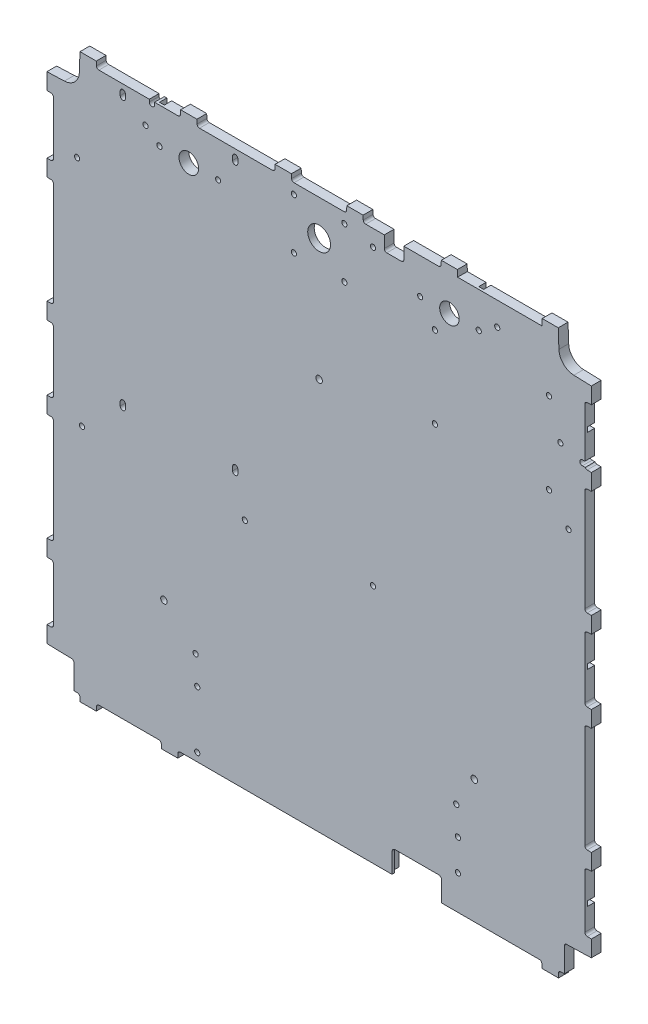
SolidWorks part; units mm, degrees
ref_plane "Alzado" through (0, 0, 0) normal (0, 0, 1) x (1, 0, 0)
ref_plane "Planta" through (0, 0, 0) normal (0, 1, 0) x (1, 0, 0)
ref_plane "Vista lateral" through (0, 0, 0) normal (1, 0, 0) x (0, 0, -1)
ref_plane "Plano1" through (0, 0, -3) normal (0, 0, -1) x (-1, 0, 0)
sketch "Croquis1" plane through (0, 0, -3) normal (0, 0, -1) x (-1, 0, 0)
  line L0 (-167.1, -152) -> (-154.0079, -152.4572)
  line L1 (-154.0079, -152.4572) -> (154.0079, -152.4572)
  line L2 (154.0079, -152.4572) -> (167.1, -152)
  line L3 (167.1, -152) -> (167.1, 172.8)
  line L4 (167.1, 172.8) -> (-167.1, 172.8)
  line L5 (-167.1, 172.8) -> (-167.1, -152)
  dimension "D1" = 13.0921
  dimension "D2" = 321.1079
  dimension "D3" = 334.2
  dimension "D4" = 0.4572
  dimension "D5" = 325.2572
extrude "Saliente-Extruir1" add sketch "Croquis1" against normal blind 6
sketch "Croquis2" plane through (0, -152.4572, 0) normal (0, -1, 0) x (1, 0, 0)
  line L0 (-150.5, 3) -> (150.5, 3)
  line L1 (150.5, 3) -> (150.5, -3)
  line L2 (150.5, -3) -> (-150.5, -3)
  line L3 (-150.5, -3) -> (-150.5, 3)
  line L4 (154.0079, 3) -> (154.0079, -3) construction
  line L5 (154.0079, -3) -> (-154.0079, -3) construction
  dimension "D1" = 3.5079
  dimension "D2" = 304.5079
  dimension "D3" = 6
extrude "Saliente-Extruir2" add sketch "Croquis2" along normal blind 20.3428
sketch "Croquis3" plane through (0, 0, 3) normal (0, 0, 1) x (1, 0, 0)
  line L0 (-136.6603, -172.8) -> (-96.9397, -172.8)
  line L1 (-96.9397, -172.8) -> (-96.9397, -168.8)
  line L2 (-96.9397, -168.8) -> (-136.6603, -168.8)
  line L3 (-136.6603, -168.8) -> (-136.6603, -172.8)
  line L4 (-167.1, -152) -> (-167.1, 172.8) construction
  line L5 (-167.1, 172.8) -> (167.1, 172.8) construction
  dimension "D1" = 30.4397
  dimension "D2" = 70.1603
  dimension "D3" = 341.6
  dimension "D4" = 345.6
extrude "Cortar-Extruir1" cut sketch "Croquis3" against normal through all
sketch "Croquis4" plane through (0, 0, 3) normal (0, 0, 1) x (1, 0, 0)
  line L0 (-167.1, -106.1397) -> (-167.1, -141.8603)
  line L1 (-167.1, -141.8603) -> (-163.1, -141.8603)
  line L2 (-163.1, -141.8603) -> (-163.1, -106.1397)
  line L3 (-163.1, -106.1397) -> (-167.1, -106.1397)
  line L4 (-136.6603, -168.8) -> (-136.6603, -172.8) construction
  line L5 (150.5, -172.8) -> (-96.9397, -172.8) construction
  dimension "D1" = 26.4397
  dimension "D2" = 30.4397
  dimension "D3" = 30.9397
  dimension "D4" = 66.6603
extrude "Cortar-Extruir2" cut sketch "Croquis4" against normal through all
sketch "Croquis5" plane through (0, 0, 3) normal (0, 0, 1) x (1, 0, 0)
  line L0 (-167.1, 19.8603) -> (-167.1, -19.8603)
  line L1 (-167.1, -19.8603) -> (-163.1, -19.8603)
  line L2 (-163.1, -19.8603) -> (-163.1, 19.8603)
  line L3 (-163.1, 19.8603) -> (-167.1, 19.8603)
  line L4 (-167.1, -152) -> (-167.1, -141.8603) construction
  line L5 (-136.6603, -172.8) -> (-150.5, -172.8) construction
  dimension "D1" = 4
  dimension "D2" = 152.9397
  dimension "D3" = 192.6603
extrude "Cortar-Extruir3" cut sketch "Croquis5" against normal through all
sketch "Croquis6" plane through (0, 0, 3) normal (0, 0, 1) x (1, 0, 0)
  line L0 (-167.1, 141.8603) -> (-167.1, 106.1397)
  line L1 (-167.1, 106.1397) -> (-163.1, 106.1397)
  line L2 (-163.1, 106.1397) -> (-163.1, 141.8603)
  line L3 (-163.1, 141.8603) -> (-167.1, 141.8603)
  line L4 (-167.1, -152) -> (-167.1, -141.8603) construction
  line L5 (-150.5, -152.4572) -> (-154.0079, -152.4572) construction
  dimension "D1" = 4
  dimension "D2" = 258.5969
  dimension "D3" = 294.3175
extrude "Cortar-Extruir4" cut sketch "Croquis6" against normal through all
sketch "Croquis7" plane through (0, 0, 3) normal (0, 0, 1) x (1, 0, 0)
  line L0 (-85, 172.8) -> (-136.8, 172.8)
  line L1 (-136.8, 172.8) -> (-136.8, 168.8)
  line L2 (-136.8, 168.8) -> (-85, 168.8)
  line L3 (-85, 168.8) -> (-85, 172.8)
  line L4 (-167.1, 19.8603) -> (-167.1, 106.1397) construction
  line L5 (-167.1, -141.8603) -> (-163.1, -141.8603) construction
  dimension "D1" = 30.3
  dimension "D2" = 82.1
  dimension "D3" = 310.6603
  dimension "D4" = 314.6603
extrude "Cortar-Extruir5" cut sketch "Croquis7" against normal through all
sketch "Croquis8" plane through (0, 0, -3) normal (0, 0, -1) x (-1, 0, 0)
  line L0 (-167.1, 124.5) -> (-156.779, 124.5)
  line L1 (-155.3, 123.25) -> (-153.9, 123.25)
  line L2 (-152.421, 124.5) -> (-152.421, 127.5)
  line L3 (-153.9, 128.75) -> (-155.3, 128.75)
  line L4 (-156.779, 127.5) -> (-167.1, 127.5)
  line L5 (-167.1, 127.5) -> (-167.1, 124.5)
  line L6 (-167.1, 172.8) -> (-167.1, -152) construction
  line L7 (85, 172.8) -> (-167.1, 172.8) construction
  arc A0 (-156.779, 124.5) -> (-155.3, 123.25) centre (-155.3, 124.75) ccw
  arc A1 (-153.9, 123.25) -> (-152.421, 124.5) centre (-153.9, 124.75) ccw
  arc A2 (-152.421, 127.5) -> (-153.9, 128.75) centre (-153.9, 127.25) ccw
  arc A3 (-155.3, 128.75) -> (-156.779, 127.5) centre (-155.3, 127.25) ccw
  dimension "D1" = 1.5
  dimension "D2" = 1.5
  dimension "D3" = 14.679
  dimension "D4" = 45.55
extrude "Cortar-Extruir6" cut sketch "Croquis8" against normal blind 4.5
sketch "Croquis9" plane through (0, 0, -3) normal (0, 0, -1) x (-1, 0, 0)
  line L0 (-115.3, -172.8) -> (-115.3, -162.479)
  line L1 (-114.05, -161) -> (-114.05, -159.6)
  line L2 (-115.3, -158.121) -> (-118.3, -158.121)
  line L3 (-119.55, -159.6) -> (-119.55, -161)
  line L4 (-118.3, -162.479) -> (-118.3, -172.8)
  line L5 (-118.3, -172.8) -> (-115.3, -172.8)
  line L6 (-167.1, 124.5) -> (-167.1, -152) construction
  line L7 (96.9397, -172.8) -> (-150.5, -172.8) construction
  arc A0 (-115.3, -162.479) -> (-114.05, -161) centre (-115.55, -161) ccw
  arc A1 (-114.05, -159.6) -> (-115.3, -158.121) centre (-115.55, -159.6) ccw
  arc A2 (-118.3, -158.121) -> (-119.55, -159.6) centre (-118.05, -159.6) ccw
  arc A3 (-119.55, -161) -> (-118.3, -162.479) centre (-118.05, -161) ccw
  dimension "D1" = 1.5
  dimension "D2" = 1.5
  dimension "D3" = 47.55
  dimension "D4" = 11.8
extrude "Cortar-Extruir7" cut sketch "Croquis9" against normal blind 4.5
sketch "Croquis10" plane through (0, 0, -3) normal (0, 0, -1) x (-1, 0, 0)
  line L0 (118.3, -168.8) -> (118.3, -162.479)
  line L1 (119.55, -161) -> (119.55, -159.6)
  line L2 (118.3, -158.121) -> (115.3, -158.121)
  line L3 (114.05, -159.6) -> (114.05, -161)
  line L4 (115.3, -162.479) -> (115.3, -168.8)
  line L5 (115.3, -168.8) -> (118.3, -168.8)
  line L6 (167.1, -152) -> (167.1, -141.8603) construction
  line L7 (150.5, -172.8) -> (136.6603, -172.8) construction
  arc A0 (118.3, -162.479) -> (119.55, -161) centre (118.05, -161) ccw
  arc A1 (119.55, -159.6) -> (118.3, -158.121) centre (118.05, -159.6) ccw
  arc A2 (115.3, -158.121) -> (114.05, -159.6) centre (115.55, -159.6) ccw
  arc A3 (114.05, -161) -> (115.3, -162.479) centre (115.55, -161) ccw
  dimension "D1" = 1.5
  dimension "D2" = 1.5
  dimension "D3" = 47.55
  dimension "D4" = 51.55
  dimension "D5" = 4
  dimension "D6" = 11.8
  dimension "D7" = 13.2
extrude "Cortar-Extruir8" cut sketch "Croquis10" against normal blind 4.5
sketch "Croquis11" plane through (0, 0, -3) normal (0, 0, -1) x (-1, 0, 0)
  line L0 (163.1, -124.5) -> (156.779, -124.5)
  line L1 (155.3, -123.25) -> (153.9, -123.25)
  line L2 (152.421, -124.5) -> (152.421, -127.5)
  line L3 (153.9, -128.75) -> (155.3, -128.75)
  line L4 (156.779, -127.5) -> (163.1, -127.5)
  line L5 (163.1, -127.5) -> (163.1, -124.5)
  line L6 (167.1, 141.8603) -> (167.1, 172.8) construction
  line L7 (167.1, 172.8) -> (136.8, 172.8) construction
  arc A0 (156.779, -124.5) -> (155.3, -123.25) centre (155.3, -124.75) ccw
  arc A1 (153.9, -123.25) -> (152.421, -124.5) centre (153.9, -124.75) ccw
  arc A2 (152.421, -127.5) -> (153.9, -128.75) centre (153.9, -127.25) ccw
  arc A3 (155.3, -128.75) -> (156.779, -127.5) centre (155.3, -127.25) ccw
  dimension "D1" = 1.5
  dimension "D2" = 1.5
  dimension "D3" = 4
  dimension "D4" = 296.05
  dimension "D5" = 297.3
  dimension "D6" = 300.05
extrude "Cortar-Extruir9" cut sketch "Croquis11" against normal blind 4.5
sketch "Croquis12" plane through (0, 0, -3) normal (0, 0, -1) x (-1, 0, 0)
  line L0 (163.1, 1.5) -> (156.779, 1.5)
  line L1 (155.3, 2.75) -> (153.9, 2.75)
  line L2 (152.421, 1.5) -> (152.421, -1.5)
  line L3 (153.9, -2.75) -> (155.3, -2.75)
  line L4 (156.779, -1.5) -> (163.1, -1.5)
  line L5 (163.1, -1.5) -> (163.1, 1.5)
  line L6 (167.1, 141.8603) -> (167.1, 172.8) construction
  line L7 (167.1, 172.8) -> (136.8, 172.8) construction
  arc A0 (156.779, 1.5) -> (155.3, 2.75) centre (155.3, 1.25) ccw
  arc A1 (153.9, 2.75) -> (152.421, 1.5) centre (153.9, 1.25) ccw
  arc A2 (152.421, -1.5) -> (153.9, -2.75) centre (153.9, -1.25) ccw
  arc A3 (155.3, -2.75) -> (156.779, -1.5) centre (155.3, -1.25) ccw
  dimension "D1" = 1.5
  dimension "D2" = 1.5
  dimension "D3" = 4
  dimension "D4" = 170.05
  dimension "D5" = 171.3
  dimension "D6" = 174.05
extrude "Cortar-Extruir10" cut sketch "Croquis12" against normal blind 4.5
sketch "Croquis13" plane through (0, 0, -3) normal (0, 0, -1) x (-1, 0, 0)
  line L0 (163.1, 127.5) -> (156.779, 127.5)
  line L1 (155.3, 128.75) -> (153.9, 128.75)
  line L2 (152.421, 127.5) -> (152.421, 124.5)
  line L3 (153.9, 123.25) -> (155.3, 123.25)
  line L4 (156.779, 124.5) -> (163.1, 124.5)
  line L5 (163.1, 124.5) -> (163.1, 127.5)
  line L6 (167.1, 141.8603) -> (167.1, 172.8) construction
  line L7 (167.1, 172.8) -> (136.8, 172.8) construction
  arc A0 (156.779, 127.5) -> (155.3, 128.75) centre (155.3, 127.25) ccw
  arc A1 (153.9, 128.75) -> (152.421, 127.5) centre (153.9, 127.25) ccw
  arc A2 (152.421, 124.5) -> (153.9, 123.25) centre (153.9, 124.75) ccw
  arc A3 (155.3, 123.25) -> (156.779, 124.5) centre (155.3, 124.75) ccw
  dimension "D1" = 1.5
  dimension "D2" = 1.5
  dimension "D3" = 4
  dimension "D4" = 44.05
  dimension "D5" = 45.3
  dimension "D6" = 48.05
extrude "Cortar-Extruir11" cut sketch "Croquis13" against normal blind 4.5
sketch "Croquis14" plane through (0, 0, -3) normal (0, 0, -1) x (-1, 0, 0)
  line L0 (96.5, 168.8) -> (96.5, 162.479)
  line L1 (95.25, 161) -> (95.25, 159.6)
  line L2 (96.5, 158.121) -> (99.5, 158.121)
  line L3 (100.75, 159.6) -> (100.75, 161)
  line L4 (99.5, 162.479) -> (99.5, 168.8)
  line L5 (99.5, 168.8) -> (96.5, 168.8)
  line L6 (167.1, 141.8603) -> (167.1, 172.8) construction
  line L7 (167.1, 172.8) -> (136.8, 172.8) construction
  arc A0 (96.5, 162.479) -> (95.25, 161) centre (96.75, 161) ccw
  arc A1 (95.25, 159.6) -> (96.5, 158.121) centre (96.75, 159.6) ccw
  arc A2 (99.5, 158.121) -> (100.75, 159.6) centre (99.25, 159.6) ccw
  arc A3 (100.75, 161) -> (99.5, 162.479) centre (99.25, 161) ccw
  dimension "D1" = 1.5
  dimension "D2" = 1.5
  dimension "D3" = 66.35
  dimension "D4" = 67.6
  dimension "D5" = 70.6
  dimension "D6" = 4
  dimension "D7" = 11.8
  dimension "D8" = 14.679
extrude "Cortar-Extruir12" cut sketch "Croquis14" against normal blind 4.5
sketch "Croquis15" plane through (0, 0, 3) normal (0, 0, 1) x (1, 0, 0)
  line L0 (44.75, -172.8) -> (136.8, -172.8)
  line L1 (136.8, -172.8) -> (136.8, -168.8)
  line L2 (136.8, -168.8) -> (75.25, -168.8)
  line L3 (75.25, -168.8) -> (75.25, -154.7)
  line L4 (75.25, -154.7) -> (44.75, -154.7)
  line L5 (44.75, -154.7) -> (44.75, -172.8)
  line L6 (-167.1, -106.1397) -> (-167.1, -19.8603) construction
  line L7 (-163.1, -106.1397) -> (-167.1, -106.1397) construction
  dimension "D1" = 211.85
  dimension "D2" = 242.35
  dimension "D3" = 303.9
  dimension "D4" = 48.5603
  dimension "D5" = 62.6603
  dimension "D6" = 66.6603
extrude "Cortar-Extruir13" cut sketch "Croquis15" against normal through all
sketch "Croquis16" plane through (0, -168.8, 0) normal (0, -1, 0) x (1, 0, 0)
  line L0 (77, -3) -> (77, 1.5)
  line L1 (77, 1.5) -> (75.25, 1.5)
  line L2 (75.25, 1.5) -> (75.25, -3)
  line L3 (75.25, -3) -> (77, -3)
  line L4 (118.3, -3) -> (118.3, 1.5) construction
  line L5 (115.3, 1.5) -> (118.3, 1.5) construction
  dimension "D1" = 41.3
  dimension "D2" = 43.05
  dimension "D3" = 4.5
extrude "Cortar-Extruir14" cut sketch "Croquis16" against normal blind 14.1
sketch "Croquis17" plane through (0, 0, -3) normal (0, 0, -1) x (-1, 0, 0)
  line L0 (86.6603, -172.8) -> (86.6603, -168.8)
  line L1 (86.6603, -168.8) -> (-44.75, -168.8)
  line L2 (-44.75, -168.8) -> (-44.75, -172.8)
  line L3 (-44.75, -172.8) -> (86.6603, -172.8)
  line L4 (167.1, -152) -> (167.1, -141.8603) construction
  line L5 (150.5, -172.8) -> (136.6603, -172.8) construction
  dimension "D1" = 80.4397
  dimension "D2" = 211.85
  dimension "D3" = 4
extrude "Cortar-Extruir15" cut sketch "Croquis17" against normal through all
sketch "Croquis18" plane through (0, -168.8, 0) normal (0, -1, 0) x (1, 0, 0)
  line L0 (44.75, -3) -> (44.75, 1.5)
  line L1 (44.75, 1.5) -> (43, 1.5)
  line L2 (43, 1.5) -> (43, -3)
  line L3 (43, -3) -> (44.75, -3)
  line L4 (-86.6603, 3) -> (-86.6603, -3) construction
  line L5 (-86.6603, -3) -> (44.75, -3) construction
  dimension "D1" = 129.6603
  dimension "D2" = 131.4103
  dimension "D3" = 4.5
extrude "Cortar-Extruir16" cut sketch "Croquis18" against normal blind 14.1
sketch "Croquis19" plane through (0, 0, -3) normal (0, 0, -1) x (-1, 0, 0)
  line L0 (99.3375, 158.121) -> (96.6625, 158.121)
  line L1 (167.1, -152) -> (167.1, -141.8603) construction
  line L2 (150.5, -172.8) -> (136.6603, -172.8) construction
  arc A0 (96.6625, 158.121) -> (99.3375, 158.121) centre (98, 158.8) ccw
  dimension "D1" = 1.5
  dimension "D2" = 67.7625
  dimension "D3" = 69.1
  dimension "D4" = 330.921
extrude "Cortar-Extruir17" cut sketch "Croquis19" against normal blind 4.5
sketch "Croquis20" plane through (0, 0, -3) normal (0, 0, -1) x (-1, 0, 0)
  line L0 (152.421, 124.6625) -> (152.421, 127.3375)
  line L1 (-167.1, 172.8) -> (-167.1, 127.5) construction
  line L2 (85, 172.8) -> (-167.1, 172.8) construction
  arc A0 (152.421, 127.3375) -> (152.421, 124.6625) centre (153.1, 126) ccw
  dimension "D1" = 1.5
  dimension "D2" = 319.521
  dimension "D3" = 320.2
  dimension "D4" = 45.4625
extrude "Cortar-Extruir18" cut sketch "Croquis20" against normal blind 4.5
sketch "Croquis21" plane through (0, 0, -3) normal (0, 0, -1) x (-1, 0, 0)
  line L0 (152.421, -1.3375) -> (152.421, 1.3375)
  line L1 (167.1, 141.8603) -> (167.1, 172.8) construction
  line L2 (167.1, 172.8) -> (136.8, 172.8) construction
  arc A0 (152.421, 1.3375) -> (152.421, -1.3375) centre (153.1, 0) ccw
  dimension "D1" = 1.5
  dimension "D2" = 14
  dimension "D3" = 14.679
  dimension "D4" = 171.4625
extrude "Cortar-Extruir19" cut sketch "Croquis21" against normal blind 4.5
sketch "Croquis22" plane through (0, 0, -3) normal (0, 0, -1) x (-1, 0, 0)
  line L0 (152.421, -127.3375) -> (152.421, -124.6625)
  line L1 (167.1, 141.8603) -> (167.1, 172.8) construction
  line L2 (167.1, 172.8) -> (136.8, 172.8) construction
  arc A0 (152.421, -124.6625) -> (152.421, -127.3375) centre (153.1, -126) ccw
  dimension "D1" = 1.5
  dimension "D2" = 14
  dimension "D3" = 14.679
  dimension "D4" = 297.4625
extrude "Cortar-Extruir20" cut sketch "Croquis22" against normal blind 4.5
sketch "Croquis23" plane through (0, 0, -3) normal (0, 0, -1) x (-1, 0, 0)
  line L0 (115.4625, -158.121) -> (118.1375, -158.121)
  line L1 (167.1, 141.8603) -> (167.1, 172.8) construction
  line L2 (167.1, 172.8) -> (136.8, 172.8) construction
  arc A0 (118.1375, -158.121) -> (115.4625, -158.121) centre (116.8, -158.8) ccw
  dimension "D1" = 1.5
  dimension "D2" = 48.9625
  dimension "D3" = 50.3
  dimension "D4" = 330.921
extrude "Cortar-Extruir21" cut sketch "Croquis23" against normal blind 4.5
sketch "Croquis24" plane through (0, 0, 3) normal (0, 0, 1) x (1, 0, 0)
  line L0 (-27, 172.8) -> (-75, 172.8)
  line L1 (-75, 172.8) -> (-75, 168.8)
  line L2 (-75, 168.8) -> (-27, 168.8)
  line L3 (-27, 168.8) -> (-27, 172.8)
  line L4 (-167.1, 141.8603) -> (-167.1, 172.8) construction
  line L5 (-167.1, 172.8) -> (-136.8, 172.8) construction
  dimension "D1" = 92.1
  dimension "D2" = 140.1
  dimension "D3" = 4
extrude "Cortar-Extruir22" cut sketch "Croquis24" against normal through all
sketch "Croquis25" plane through (0, 0, 3) normal (0, 0, 1) x (1, 0, 0)
  line L0 (-17, 172.8) -> (-17, 168.8)
  line L1 (-17, 168.8) -> (17, 168.8)
  line L2 (17, 168.8) -> (17, 172.8)
  line L3 (17, 172.8) -> (-17, 172.8)
  line L4 (-167.1, 141.8603) -> (-167.1, 172.8) construction
  line L5 (-167.1, 172.8) -> (-136.8, 172.8) construction
  dimension "D1" = 150.1
  dimension "D2" = 184.1
  dimension "D3" = 4
extrude "Cortar-Extruir23" cut sketch "Croquis25" against normal through all
sketch "Croquis26" plane through (0, 0, 3) normal (0, 0, 1) x (1, 0, 0)
  line L0 (27, 172.8) -> (27, 168.8)
  line L1 (27, 168.8) -> (40, 168.8)
  line L2 (40, 168.8) -> (40, 160)
  line L3 (40, 160) -> (52, 160)
  line L4 (52, 160) -> (52, 168.8)
  line L5 (52, 168.8) -> (74.8603, 168.8)
  line L6 (74.8603, 168.8) -> (74.8603, 172.8)
  line L7 (74.8603, 172.8) -> (27, 172.8)
  line L8 (-167.1, -106.1397) -> (-167.1, -19.8603) construction
  line L9 (-163.1, -106.1397) -> (-167.1, -106.1397) construction
  dimension "D1" = 194.1
  dimension "D2" = 207.1
  dimension "D3" = 219.1
  dimension "D4" = 241.9603
  dimension "D5" = 266.1397
  dimension "D6" = 274.9397
  dimension "D7" = 278.9397
extrude "Cortar-Extruir24" cut sketch "Croquis26" against normal through all
sketch "Croquis27" plane through (0, 0, 3) normal (0, 0, 1) x (1, 0, 0)
  line L0 (167.1, 172.8) -> (146.8, 172.8)
  line L1 (146.8, 172.8) -> (147.5264, 152)
  line L2 (147.5264, 152) -> (167.1, 152)
  line L3 (167.1, 152) -> (167.1, 172.8)
  line L4 (-167.1, 19.8603) -> (-167.1, 106.1397) construction
  line L5 (-163.1, 19.8603) -> (-167.1, 19.8603) construction
  dimension "D1" = 313.9
  dimension "D2" = 314.6264
  dimension "D3" = 334.2
  dimension "D4" = 132.1397
  dimension "D5" = 152.9397
extrude "Cortar-Extruir25" cut sketch "Croquis27" against normal through all
sketch "Croquis28" plane through (0, 0, 3) normal (0, 0, 1) x (1, 0, 0)
  line L0 (167.1, 106.82) -> (167.1, 142)
  line L1 (167.1, 142) -> (163.1, 142)
  line L2 (163.1, 142) -> (163.1, 110.02)
  line L3 (163.1, 110.02) -> (161.6, 110.02)
  line L4 (161.6, 106.82) -> (167.1, 106.82)
  line L5 (-167.1, 141.8603) -> (-167.1, 172.8) construction
  line L6 (-167.1, 172.8) -> (-136.8, 172.8) construction
  arc A0 (161.6, 110.02) -> (161.6, 106.82) centre (161.6, 108.42) ccw
  dimension "D1" = 1.6
  dimension "D2" = 328.7
  dimension "D3" = 330.2
  dimension "D4" = 334.2
  dimension "D5" = 30.8
  dimension "D6" = 64.38
extrude "Cortar-Extruir26" cut sketch "Croquis28" against normal through all
sketch "Croquis29" plane through (0, 0, 3) normal (0, 0, 1) x (1, 0, 0)
  line L0 (164.5477, 106.0891) -> (167.1, 106)
  line L1 (167.1, 106) -> (167.1, 106.82)
  line L2 (167.1, 106.82) -> (163.3117, 106.82)
  line L3 (-167.1, 141.8603) -> (-167.1, 172.8) construction
  line L4 (-167.1, 172.8) -> (-136.8, 172.8) construction
  arc A0 (163.3117, 106.82) -> (164.5477, 106.0891) centre (164.6, 107.5882) ccw
  dimension "D1" = 1.5
  dimension "D2" = 330.4117
  dimension "D3" = 331.6477
  dimension "D4" = 331.7
  dimension "D5" = 334.2
  dimension "D6" = 65.2118
extrude "Cortar-Extruir27" cut sketch "Croquis29" against normal through all
sketch "Croquis30" plane through (0, 0, 3) normal (0, 0, 1) x (1, 0, 0)
  line L0 (-150.5, -172.8) -> (-146.9397, -172.8)
  line L1 (-146.9397, -172.8) -> (-146.9397, -168.8)
  line L2 (-146.9397, -168.8) -> (-150.5, -168.8)
  line L3 (-150.5, -168.8) -> (-150.5, -172.8)
  line L4 (-167.1, 141.8603) -> (-167.1, 172.8) construction
  line L5 (-167.1, 172.8) -> (-136.8, 172.8) construction
  dimension "D1" = 16.6
  dimension "D2" = 20.1603
  dimension "D3" = 341.6
  dimension "D4" = 345.6
extrude "Cortar-Extruir28" cut sketch "Croquis30" against normal through all
sketch "Croquis31" plane through (0, 0, 3) normal (0, 0, 1) x (1, 0, 0)
  line L0 (-167.1, -30.1397) -> (-167.1, -95.8603)
  line L1 (-167.1, -95.8603) -> (-163.1, -95.8603)
  line L2 (-163.1, -95.8603) -> (-163.1, -30.1397)
  line L3 (-163.1, -30.1397) -> (-167.1, -30.1397)
  line L4 (-150.5, -168.8) -> (-150.5, -152.4572) construction
  line L5 (-136.6603, -172.8) -> (-146.9397, -172.8) construction
  dimension "D1" = 12.6
  dimension "D2" = 16.6
  dimension "D3" = 76.9397
  dimension "D4" = 142.6603
extrude "Cortar-Extruir29" cut sketch "Croquis31" against normal through all
sketch "Croquis32" plane through (0, 0, 3) normal (0, 0, 1) x (1, 0, 0)
  line L0 (-167.1, 95.8603) -> (-167.1, 30.1397)
  line L1 (-167.1, 30.1397) -> (-163.1, 30.1397)
  line L2 (-163.1, 30.1397) -> (-163.1, 95.8603)
  line L3 (-163.1, 95.8603) -> (-167.1, 95.8603)
  line L4 (-167.1, -152) -> (-167.1, -141.8603) construction
  line L5 (-136.6603, -172.8) -> (-146.9397, -172.8) construction
  dimension "D1" = 4
  dimension "D2" = 202.9397
  dimension "D3" = 268.6603
extrude "Cortar-Extruir30" cut sketch "Croquis32" against normal through all
mirror "Simetría1" about plane through (0, 0, 0) normal (1, 0, 0) of "Cortar-Extruir2", "Cortar-Extruir3", "Cortar-Extruir5", "Cortar-Extruir9", "Cortar-Extruir10", "Cortar-Extruir12", "Cortar-Extruir17", "Cortar-Extruir18", "Cortar-Extruir19", "Cortar-Extruir20", "Cortar-Extruir21", "Cortar-Extruir28", "Cortar-Extruir29", "Cortar-Extruir30"
sketch "Croquis34" plane through (0, 0, 3) normal (0, 0, 1) x (1, 0, 0)
  line L0 (-167.1, 172.8) -> (-167.1, 152)
  line L1 (-167.1, 152) -> (-146.8, 152.7089)
  line L2 (-146.8, 152.7089) -> (-146.8, 172.8)
  line L3 (-146.8, 172.8) -> (-167.1, 172.8)
  line L4 (-167.1, 141.8603) -> (-167.1, 172.8) construction
  line L5 (-167.1, 172.8) -> (-136.8, 172.8) construction
  dimension "D1" = 20.3
  dimension "D2" = 20.0911
  dimension "D3" = 20.8
extrude "Cortar-Extruir31" cut sketch "Croquis34" against normal through all
sketch "Croquis35" plane through (0, 0, 3) normal (0, 0, 1) x (1, 0, 0)
  line L0 (-101.02, 168.8) -> (-104.22, 168.8)
  line L1 (-104.22, 168.8) -> (-104.22, 167.3)
  line L2 (-101.02, 167.3) -> (-101.02, 168.8)
  line L3 (-167.1, -152) -> (-167.1, -141.8603) construction
  line L4 (-136.6603, -172.8) -> (-146.9397, -172.8) construction
  arc A0 (-104.22, 167.3) -> (-101.02, 167.3) centre (-102.62, 167.3) ccw
  dimension "D1" = 1.6
  dimension "D2" = 64.48
  dimension "D3" = 340.1
  dimension "D4" = 341.6
extrude "Cortar-Extruir32" cut sketch "Croquis35" against normal through all
sketch "Croquis36" plane through (0, 0, -3) normal (0, 0, -1) x (-1, 0, 0)
  line L0 (49.9, -0.75) -> (49.9, -3.25)
  line L1 (53.1, -3.25) -> (53.1, -0.75)
  line L2 (101.02, 168.8) -> (101.02, 167.3) construction
  line L3 (85, 172.8) -> (75, 172.8) construction
  arc A0 (49.9, -3.25) -> (53.1, -3.25) centre (51.5, -3.25) ccw
  arc A1 (53.1, -0.75) -> (49.9, -0.75) centre (51.5, -0.75) ccw
  dimension "D1" = 1.6
  dimension "D2" = 49.52
  dimension "D3" = 173.55
  dimension "D4" = 176.05
extrude "Cortar-Extruir33" cut sketch "Croquis36" against normal through all
sketch "Croquis37" plane through (0, 0, -3) normal (0, 0, -1) x (-1, 0, 0)
  line L0 (118.9, -0.75) -> (118.9, -3.25)
  line L1 (122.1, -3.25) -> (122.1, -0.75)
  line L2 (101.02, 168.8) -> (101.02, 167.3) construction
  line L3 (85, 172.8) -> (75, 172.8) construction
  arc A0 (118.9, -3.25) -> (122.1, -3.25) centre (120.5, -3.25) ccw
  arc A1 (122.1, -0.75) -> (118.9, -0.75) centre (120.5, -0.75) ccw
  dimension "D1" = 1.6
  dimension "D2" = 19.48
  dimension "D3" = 173.55
  dimension "D4" = 176.05
extrude "Cortar-Extruir34" cut sketch "Croquis37" against normal through all
sketch "Croquis38" plane through (0, 0, -3) normal (0, 0, -1) x (-1, 0, 0)
  line L0 (122.1, 161.75) -> (122.1, 164.25)
  line L1 (118.9, 164.25) -> (118.9, 161.75)
  line L2 (122.1, -3.25) -> (122.1, -0.75) construction
  line L3 (-153.9, -128.75) -> (-155.3, -128.75) construction
  arc A0 (122.1, 164.25) -> (118.9, 164.25) centre (120.5, 164.25) ccw
  arc A1 (118.9, 161.75) -> (122.1, 161.75) centre (120.5, 161.75) ccw
  dimension "D1" = 1.6
  dimension "D2" = 1.6
  dimension "D3" = 290.5
  dimension "D4" = 293
extrude "Cortar-Extruir35" cut sketch "Croquis38" against normal through all
sketch "Croquis39" plane through (0, 0, 3) normal (0, 0, 1) x (1, 0, 0)
  line L0 (-53.1, 164.25) -> (-53.1, 161.75)
  line L1 (-49.9, 161.75) -> (-49.9, 164.25)
  line L2 (-167.1, -152) -> (-167.1, -141.8603) construction
  line L3 (-136.6603, -172.8) -> (-146.9397, -172.8) construction
  arc A0 (-53.1, 161.75) -> (-49.9, 161.75) centre (-51.5, 161.75) ccw
  arc A1 (-49.9, 164.25) -> (-53.1, 164.25) centre (-51.5, 164.25) ccw
  dimension "D1" = 1.6
  dimension "D2" = 115.6
  dimension "D3" = 334.55
  dimension "D4" = 337.05
extrude "Cortar-Extruir36" cut sketch "Croquis39" against normal through all
sketch "Croquis40" plane through (0, 0, -3) normal (0, 0, -1) x (-1, 0, 0)
  line L0 (86.9, -127.8) -> (86.9, -125.8)
  line L1 (83.7, -125.8) -> (83.7, -127.8)
  line L2 (122.1, 161.75) -> (122.1, 164.25) construction
  line L3 (85, 172.8) -> (75, 172.8) construction
  arc A0 (83.7, -127.8) -> (86.9, -127.8) centre (85.3, -127.8) ccw
  arc A1 (86.9, -125.8) -> (83.7, -125.8) centre (85.3, -125.8) ccw
  dimension "D1" = 1.6
  dimension "D2" = 36.8
  dimension "D3" = 298.6
  dimension "D4" = 300.6
extrude "Cortar-Extruir37" cut sketch "Croquis40" against normal blind 4.5
sketch "Croquis41" plane through (0, 0, -3) normal (0, 0, -1) x (-1, 0, 0)
  line L0 (-92.1, -127.8) -> (-92.1, -125.8)
  line L1 (-95.3, -125.8) -> (-95.3, -127.8)
  line L2 (122.1, 161.75) -> (122.1, 164.25) construction
  line L3 (85, 172.8) -> (75, 172.8) construction
  arc A0 (-95.3, -127.8) -> (-92.1, -127.8) centre (-93.7, -127.8) ccw
  arc A1 (-92.1, -125.8) -> (-95.3, -125.8) centre (-93.7, -125.8) ccw
  dimension "D1" = 1.6
  dimension "D2" = 215.8
  dimension "D3" = 298.6
  dimension "D4" = 300.6
extrude "Cortar-Extruir38" cut sketch "Croquis41" against normal blind 4.5
sketch "Croquis42" plane through (0, -154.7, 0) normal (0, -1, 0) x (1, 0, 0)
  line L0 (50, 1.5) -> (50, -3)
  line L1 (50, -3) -> (70, -3)
  line L2 (70, -3) -> (70, 1.5)
  line L3 (70, 1.5) -> (50, 1.5)
  line L4 (77, -3) -> (77, 1.5) construction
  line L5 (43, -3) -> (77, -3) construction
  dimension "D1" = 7
  dimension "D2" = 27
  dimension "D3" = 4.5
extrude "Cortar-Extruir39" cut sketch "Croquis42" against normal blind 15
sketch "Croquis43" plane through (0, 0, -3) normal (0, 0, -1) x (-1, 0, 0)
  line L0 (27.1, 19.8) -> (27.1, 17.8)
  line L1 (31.1, 17.8) -> (31.1, 19.8)
  line L2 (167.1, -152) -> (167.1, -141.8603) construction
  line L3 (146.9397, -172.8) -> (136.6603, -172.8) construction
  arc A0 (31.1, 19.8) -> (27.1, 19.8) centre (29.1, 19.8) ccw
  arc A1 (27.1, 17.8) -> (31.1, 17.8) centre (29.1, 17.8) ccw
  dimension "D1" = 2
  dimension "D2" = 138
  dimension "D3" = 190.6
  dimension "D4" = 192.6
extrude "Cortar-Extruir40" cut sketch "Croquis43" against normal blind 4.5
draft "Ángulo de salida1" type of draft neutral plane draft angle 1.443 faces to draft 1 face at (-151.377, -152.4572, 0.75) neutral plane through (-150.5, -172.8, -3) neutral plane normal (-1, 0, 0) parameters "D1"=1.443
draft "Ángulo de salida2" type of draft neutral plane draft angle 2 faces to draft 1 face at (-146.9397, -170.8, 0) neutral plane through (-146.9397, -168.8, -3) neutral plane normal (0, -1, 0) parameters "D1"=2
draft "Ángulo de salida3" type of draft neutral plane draft angle 2 faces to draft 1 face at (-86.6603, -170.8, 0) neutral plane through (-86.6603, -168.8, 3) neutral plane normal (0, -1, 0) parameters "D1"=2
draft "Ángulo de salida4" type of draft neutral plane draft angle 1.443 faces to draft 1 face at (153.1309, -152.4572, -0.75) neutral plane through (150.5, -172.8, 3) neutral plane normal (1, 0, 0) parameters "D1"=1.443
draft "Ángulo de salida5" type of draft neutral plane draft angle 2 faces to draft 1 face at (74.8603, 170.8, 0) neutral plane through (52, 168.8, -3) neutral plane normal (0, 1, 0) parameters "D1"=2
draft "Ángulo de salida6" type of draft neutral plane draft angle 2 faces to draft 2 face at (-146.8, 162.7544, 0) face at (-136.8, 170.8, 0) neutral plane through (-167.1, 172.8, 3) neutral plane normal (0, 1, 0) parameters "D1"=2
draft "Ángulo de salida7" type of draft neutral plane draft angle 2 faces to draft 2 face at (-165.1, 95.8603, 0) face at (-165.1, 30.1397, 0) neutral plane through (-163.1, 30.1397, -3) neutral plane normal (-1, 0, 0) parameters "D1"=2
draft "Ángulo de salida8" type of draft neutral plane draft angle 2 faces to draft 2 face at (-165.1, -30.1397, 0) face at (-165.1, -95.8603, 0) neutral plane through (-163.1, -95.8603, -3) neutral plane normal (-1, 0, 0) parameters "D1"=2
draft "Ángulo de salida9" type of draft neutral plane draft angle 2 faces to draft 2 face at (165.1, -95.8603, 0) face at (165.1, -30.1397, 0) neutral plane through (163.1, -95.8603, -3) neutral plane normal (1, 0, 0) parameters "D1"=2
draft "Ángulo de salida10" type of draft neutral plane draft angle 2 faces to draft 2 face at (165.1, 30.1397, 0) face at (165.1, 95.8603, 0) neutral plane through (163.1, 30.1397, -3) neutral plane normal (1, 0, 0) parameters "D1"=2
draft "Ángulo de salida11" type of draft neutral plane draft angle 2 faces to draft 2 face at (165.1, 142, 0) face at (157.3132, 152, 0) neutral plane through (167.1, 172.8, 3) neutral plane normal (1, 0, 0) parameters "D1"=2
draft "Ángulo de salida12" type of draft neutral plane draft angle 2 faces to draft 2 face at (27, 170.8, 0) face at (17, 170.8, 0) neutral plane through (-167.1, 172.8, 3) neutral plane normal (0, 1, 0) parameters "D1"=2
draft "Ángulo de salida13" type of draft neutral plane draft angle 2 faces to draft 2 face at (-27, 170.8, 0) face at (-17, 170.8, 0) neutral plane through (-167.1, 172.8, 3) neutral plane normal (0, 1, 0) parameters "D1"=2
draft "Ángulo de salida14" type of draft neutral plane draft angle 2 faces to draft 2 face at (-85, 170.8, 0) face at (-75, 170.8, 0) neutral plane through (-167.1, 172.8, 3) neutral plane normal (0, 1, 0) parameters "D1"=2
draft "Ángulo de salida15" type of draft neutral plane draft angle 2 faces to draft 2 face at (-165.1, 141.8603, 0) face at (-165.1, 106.1397, 0) neutral plane through (-163.1, 106.1397, -3) neutral plane normal (-1, 0, 0) parameters "D1"=2
draft "Ángulo de salida16" type of draft neutral plane draft angle 2 faces to draft 2 face at (-165.1, 19.8603, 0) face at (-165.1, -19.8603, 0) neutral plane through (-163.1, -19.8603, -3) neutral plane normal (-1, 0, 0) parameters "D1"=2
draft "Ángulo de salida17" type of draft neutral plane draft angle 2 faces to draft 2 face at (-165.1, -106.1397, 0) face at (-165.1, -141.8603, 0) neutral plane through (-163.1, -141.8603, -3) neutral plane normal (-1, 0, 0) parameters "D1"=2
draft "Ángulo de salida18" type of draft neutral plane draft angle 2 faces to draft 2 face at (-136.6603, -170.8, 0) face at (-96.9397, -170.8, 0) neutral plane through (-96.9397, -168.8, -3) neutral plane normal (0, -1, 0) parameters "D1"=2
draft "Ángulo de salida19" type of draft neutral plane draft angle 2 faces to draft 1 face at (136.8, -170.8, 0) neutral plane through (0, -172.8, 0) neutral plane normal (0, -1, 0) parameters "D1"=2
draft "Ángulo de salida20" type of draft neutral plane draft angle 2 faces to draft 2 face at (165.1, -141.8603, 0) face at (165.1, -106.1397, 0) neutral plane through (163.1, -141.8603, -3) neutral plane normal (1, 0, 0) parameters "D1"=2
draft "Ángulo de salida21" type of draft neutral plane draft angle 2 faces to draft 2 face at (165.1, -19.8603, 0) face at (165.1, 19.8603, 0) neutral plane through (163.1, -19.8603, -3) neutral plane normal (1, 0, 0) parameters "D1"=2
draft "Ángulo de salida22" type of draft neutral plane draft angle 2 faces to draft 2 face at (85, 170.8, 0) face at (136.8, 170.8, 0) neutral plane through (136.8, 168.8, -3) neutral plane normal (0, 1, 0) parameters "D1"=2
hole_wizard "Diámetro de taladro Ø12.0 (12)1" positions "Croquis45" profile "Croquis44" hole size "Ø12.0" standard "Ansi Metric"
sketch "Croquis45" plane through (0, 0, 3) normal (0, 0, 1) x (1, 0, 0)
  point P0 (-80, 147)
sketch "Croquis44" plane through (-80, 147, 3) normal (1, 0, 0) x (0, -1, 0)
  line L0 (0, 0) -> (0, 6)
  line L1 (0, 6) -> (6, 6)
  line L2 (6, 6) -> (6, 0)
  line L5 (6, 0) -> (0, 0)
  line L11 (0, -6.35) -> (0, 107.95) construction
  dimension "Diámetro de taladro hasta el siguiente" = 12
  dimension "Profundidad de taladro hasta el siguiente" = 6
mirror "Simetría2" about plane through (0, 0, 0) normal (1, 0, 0) of "Diámetro de taladro Ø12.0 (12)1"
hole_wizard "Diámetro de taladro Ø4.0 (4)1" positions "Croquis48" profile "Croquis47" hole size "Ø4.0" standard "Ansi Metric"
sketch "Croquis48" plane through (0, 0, 3) normal (0, 0, 1) x (1, 0, 0)
  point P0 (0, 72)
  point P1 (95.2628, -93)
  point P2 (-95.2628, -93)
sketch "Croquis47" plane through (0, 72, 3) normal (1, 0, 0) x (0, -1, 0)
  line L0 (0, 0) -> (0, 6)
  line L1 (0, 6) -> (2, 6)
  line L2 (2, 6) -> (2, 0)
  line L5 (2, 0) -> (0, 0)
  line L11 (0, -6.35) -> (0, 107.95) construction
  dimension "Diámetro de taladro hasta el siguiente" = 4
  dimension "Profundidad de taladro hasta el siguiente" = 6
hole_wizard "Diámetro de taladro Ø3.2 (3.2)1" positions "Croquis50" profile "Croquis49" hole size "Ø3.2" standard "Ansi Metric"
sketch "Croquis50" plane through (0, 0, -3) normal (0, 0, -1) x (-1, 0, 0)
  point P0 (-141.1, 133.8)
  point P1 (-71.1, 133.8)
  point P2 (-141.1, 83.8)
  point P3 (-71.1, 83.8)
  point P4 (-15.5, 162.5)
  point P5 (-15.5, 131.5)
sketch "Croquis49" plane through (141.1, 133.8, -3) normal (1, 0, 0) x (0, 1, 0)
  line L0 (0, 0) -> (0, 6)
  line L1 (0, 6) -> (1.6, 6)
  line L2 (1.6, 6) -> (1.6, 0)
  line L5 (1.6, 0) -> (0, 0)
  line L11 (0, -6.35) -> (0, 107.95) construction
  dimension "Diámetro de taladro hasta el siguiente" = 3.2
  dimension "Profundidad de taladro hasta el siguiente" = 6
hole_wizard "Diámetro de taladro Ø3.2 (3.2)2" positions "Croquis52" profile "Croquis51" hole size "Ø3.2" standard "Ansi Metric"
sketch "Croquis52" plane through (0, 0, 3) normal (0, 0, 1) x (1, 0, 0)
  point P0 (148.1, 112.3)
  point P1 (-106.6, 153.8)
  point P2 (85.2, -147.75)
  point P3 (-74.8, -163.75)
  point P4 (-74.8, -128.75)
  point P5 (85.2, -128.75)
  point P6 (33.1, 158.8)
  point P7 (33.1, -21.2)
  point P8 (153.1, 68.8)
  point P9 (109.3289, 154.4)
  point P10 (-148.6, 115.6)
  point P11 (-45.6, -25.7)
  point P12 (-145.6, -25.7)
  point P13 (84.2, -111.8)
  point P14 (-75.8, -111.8)
  point P15 (-15.5, 162.5)
  point P16 (-15.5, 131.5)
sketch "Croquis51" plane through (148.1, 112.3, 3) normal (1, 0, 0) x (0, -1, 0)
  line L0 (0, 0) -> (0, 6)
  line L1 (0, 6) -> (1.6, 6)
  line L2 (1.6, 6) -> (1.6, 0)
  line L5 (1.6, 0) -> (0, 0)
  line L11 (0, -6.35) -> (0, 107.95) construction
  dimension "Diámetro de taladro hasta el siguiente" = 3.2
  dimension "Profundidad de taladro hasta el siguiente" = 6
hole_wizard "Refrentado para perno con cabeza hexagonal de M121" positions "Croquis54" profile "Croquis53" counterbore size "M12" standard "Ansi Metric"
sketch "Croquis54" plane through (0, 0, -3) normal (0, 0, -1) x (-1, 0, 0)
  point P0 (0, 147)
sketch "Croquis53" plane through (0, 147, -3) normal (1, 0, 0) x (0, 1, 0)
  line L0 (0, 0) -> (0, 6)
  line L1 (0, 6) -> (7, 6)
  line L3 (7, 6) -> (7, 2)
  line L4 (7, 2) -> (11.1, 2)
  line L5 (11.1, 2) -> (11.1, 0)
  line L7 (11.1, 0) -> (0, 0)
  line L11 (0, -6.35) -> (0, 107.95) construction
  dimension "Diámetro de taladro hasta el siguiente" = 14
  dimension "Profundidad de taladro hasta el siguiente" = 6
  dimension "Diámetro de refrentado" = 22.2
  dimension "Profundidad de refrentado" = 2
hole_wizard "Refrentado para tornillo con cabeza hexagonal de M31" positions "Croquis56" profile "Croquis55" counterbore size "M3" standard "Ansi Metric"
sketch "Croquis56" plane through (0, 0, -3) normal (0, 0, -1) x (-1, 0, 0)
  point P0 (-98, 147)
  point P1 (98, 147)
sketch "Croquis55" plane through (98, 147, -3) normal (1, 0, 0) x (0, 1, 0)
  line L0 (0, 0) -> (0, 6)
  line L1 (0, 6) -> (1.6, 6)
  line L3 (1.6, 6) -> (1.6, 2)
  line L4 (1.6, 2) -> (5, 2)
  line L5 (5, 2) -> (5, 0)
  line L7 (5, 0) -> (0, 0)
  line L11 (0, -6.35) -> (0, 107.95) construction
  dimension "Diámetro de taladro hasta el siguiente" = 3.2
  dimension "Profundidad de taladro hasta el siguiente" = 6
  dimension "Diámetro de refrentado" = 10
  dimension "Profundidad de refrentado" = 2
hole_wizard "Refrentado para tornillo con cabeza hexagonal de M2.51" positions "Croquis58" profile "Croquis57" counterbore size "M2.5" standard "Ansi Metric"
sketch "Croquis58" plane through (0, 0, -3) normal (0, 0, -1) x (-1, 0, 0)
  point P0 (-62, 147)
  point P1 (62, 147)
sketch "Croquis57" plane through (62, 147, -3) normal (1, 0, 0) x (0, 1, 0)
  line L0 (0, 0) -> (0, 6)
  line L1 (0, 6) -> (1.55, 6)
  line L3 (1.55, 6) -> (1.55, 2)
  line L4 (1.55, 2) -> (5, 2)
  line L5 (5, 2) -> (5, 0)
  line L7 (5, 0) -> (0, 0)
  line L11 (0, -6.35) -> (0, 107.95) construction
  dimension "Diámetro de taladro hasta el siguiente" = 3.1
  dimension "Profundidad de taladro hasta el siguiente" = 6
  dimension "Diámetro de refrentado" = 10
  dimension "Profundidad de refrentado" = 2
fillet "Redondeo1" radius 1.5 39 edges at (74.8603, 168.8, 0) (-85.1397, 168.8, 0) (163.1, -19.8603, 0) (-163.1, -30.1397, 0) (16.8603, 168.8, 0) (163.1, 141.8603, 0) (163.1, -141.8603, 0) (-150.5, -152.4572, 0) (-163.1, 95.8603, 0) (-27.1397, 168.8, 0) (40, 160, 0) (163.1, 30.1397, 0) (163.1, -95.8603, 0) (146.9397, -168.8, 0) (-136.6603, -168.8, 0) (-163.1, -106.1397, 0) (-163.1, 19.8603, 0) (-74.8603, 168.8, 0) (-16.8603, 168.8, 0) (70, -139.7, -0.75) (27.1397, 168.8, 0) (50, -139.7, -0.75) (52, 160, 0) (163.1, 95.8603, 0) (163.1, 19.8603, 0) (163.1, -30.1397, 0) (163.1, -106.1397, 0) (150.5, -152.4572, 0) (136.6603, -168.8, 0) (-86.6603, -168.8, 0) (-96.9397, -168.8, 0) (-146.9397, -168.8, 0) (-163.1, -141.8603, 0) (-163.1, -95.8603, 0) (-163.1, -19.8603, 0) (-163.1, 30.1397, 0) (-163.1, 106.1397, 0) (-163.1, 141.8603, 0) (-136.6603, 168.8, 0) tangent propagation no
fillet "Redondeo2" radius 2 2 edges at (75.25, -154.7, 2.25) (44.75, -154.7, 2.25) tangent propagation no
fillet "Redondeo3" radius 9.5 2 edges at (147.5025, 152.6844, 0) (-147.5025, 152.6844, 0) tangent propagation no
